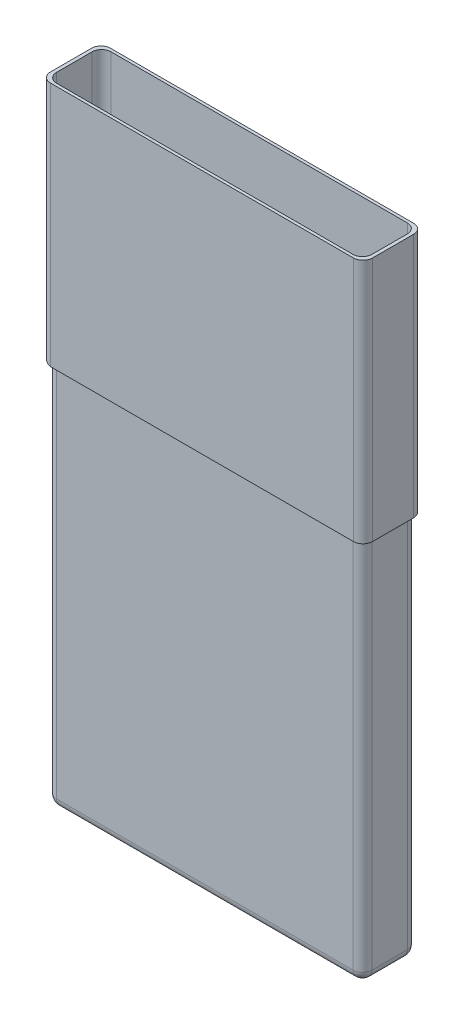
SolidWorks part; units mm, degrees
ref_plane "Alzado" through (0, 0, 0) normal (0, 0, 1) x (1, 0, 0)
ref_plane "Planta" through (0, 0, 0) normal (0, 1, 0) x (1, 0, 0)
ref_plane "Vista lateral" through (0, 0, 0) normal (1, 0, 0) x (0, 0, -1)
sketch "Croquis1" plane through (0, 0, 0) normal (0, 0, 1) x (1, 0, 0)
  line L1 (0, 0) -> (33, 0)
  line L2 (0, 0) -> (0, -53)
  line L3 (0, -53) -> (33, -53)
  line L4 (33, 0) -> (33, -53)
extrude "Saliente-Extruir1" add sketch "Croquis1" along normal blind 5.7
fillet "Redondeo1" radius 1 2 edges at (16.5, -53, 0) (16.5, -53, 5.7)
sketch "Croquis2" plane through (0, 0, 0) normal (0, 1, 0) x (1, 0, 0)
  line L0 (33, -5.7) -> (33, 0) construction
  line L1 (0, 0) -> (33, 0)
  line L2 (0, 0) -> (0, -5.7)
  line L3 (0, -5.7) -> (33, -5.7)
  line L4 (33, 0) -> (33, -5.7)
  line L5 (33, -5.7) -> (0, -5.7) construction
  line L7 (-0.3516, 0.296) -> (33.3516, 0.296)
  line L8 (-0.3516, 0.296) -> (-0.3516, -5.996)
  line L9 (-0.3516, -5.996) -> (33.3516, -5.996)
  line L10 (33.3516, 0.296) -> (33.3516, -5.996)
  line L11 (-0.3516, 0.296) -> (33.3516, -5.996) construction
  line L12 (-0.3516, -5.996) -> (33.3516, 0.296) construction
  point P9 (16.5, -2.85)
extrude "Saliente-Extruir2" add sketch "Croquis2" along normal mid plane 25.7
fillet "Redondeo2" radius 1 10 edges at (0, -52.7071, 0.2929) (0, -52.7071, 5.4071) (33, -52.7071, 0.2929) (33, -52.7071, 5.4071) (33, -53, 2.85) (0, -53, 2.85) (0, -32.425, 0) (33, -32.425, 0) (0, -32.425, 5.7) (33, -32.425, 5.7)
fillet "Redondeo3" radius 1 9 edges at (0, 6.425, 5.7) (0, 6.425, 0) (33, 6.425, 0) (33, 6.425, 5.7) (-0.3516, 0, 5.996) (-0.3516, -12.85, 2.85) (-0.3516, 0, -0.296) (33.3516, 0, 5.996) (33.3516, 0, -0.296)
sketch "Croquis5"
